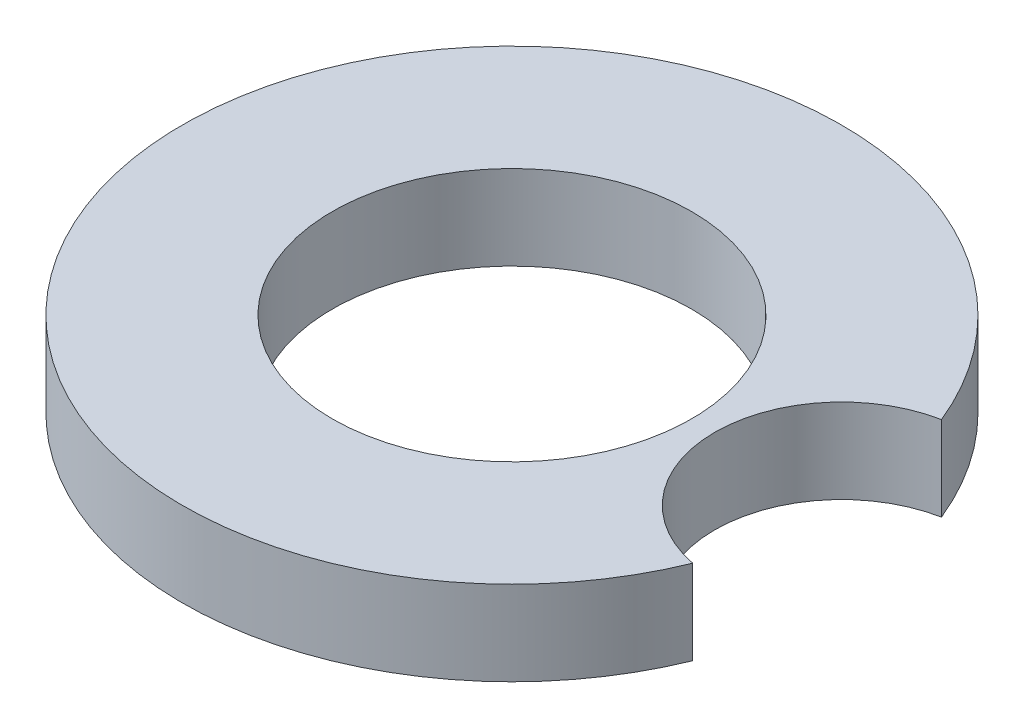
SolidWorks part; units mm, degrees
ref_plane "Front Plane" through (0, 0, 0) normal (0, 0, 1) x (1, 0, 0)
ref_plane "Top Plane" through (0, 0, 0) normal (0, 1, 0) x (1, 0, 0)
ref_plane "Right Plane" through (0, 0, 0) normal (1, 0, 0) x (0, 0, -1)
sketch "Sketch1" plane through (0, 0, 0) normal (0, 1, 0) x (1, 0, 0)
  circle A0 centre (0, 0) radius 27
  circle A1 centre (0, 0) radius 49.53
  dimension "Front_CR_ID" = 54
  dimension "Front_CR_OD" = 99.06
extrude "Boss-Extrude1" add sketch "Sketch1" along normal blind 12.7 contours A1
extrude "Cut-Extrude2" cut sketch "Sketch1<10>" along normal through all contours A0
sketch "Sketch1<10>" plane through (0, 0, 0) normal (0, 1, 0) x (1, 0, 0) same geometry as "Sketch1"
sketch "Sketch2" plane through (0, 12.7, 0) normal (0, 1, 0) x (1, 0, 0)
  circle A2 centre (49.53, 0) radius 19.05
  circle A3 centre (0, 0) radius 49.53 construction
  dimension "D1" = 38.1
extrude "Cut-Extrude3" cut sketch "Sketch2" against normal through all contours A2
ref_plane "Plane1" through (0, 6.35, 0) normal (0, -1, 0) x (-1, 0, 0)
equation "\"Motor_OD\" = 54mm"
equation "\"Aft_Section_Length\" = 30in"
equation "\"Mid_Coupler_Length\" = 12in"
equation "\"AB_Coupler_OD_Length\"= 1in"
equation "\"AB_Coupling_Section_Length\"= 0.375in"
equation "\"AB_Coupler_Length\"= \"AB_Coupler_OD_Length\" + \"AB_Coupling_Section_Length\" * 2"
equation "\"Cutout_Angle\" = 60"
equation "\"AB_Paddle_Height\" = 0.375in"
equation "\"AB_Coupler_Num_Screws\"= 4"
equation "\"Num_Cutouts\" = 4"
equation "\"AB_Coupler_OD\"= 4.024in"
equation "\"AB_Coupler_ID\"= 3.7in"
equation "\"AB_Coupler_Surface_Diameter\"= 3.899in"
equation "\"AB_Coupling_Screw_Diameter\"= 0.1065in"
equation "\"AB_Central_Bushing_Length\" = 0.75in"
equation "\"Lead_Screw_Dist\" = 2in"
equation "\"Lead_Screw_Diam\" = 0.375in"
equation "\"Lead_Screw_Length\" = \"Mid_Coupler_Length\" + 2*0.375in + 2*0.5in"
equation "\"Paddle_Pin_Offset\" = 0.25in"
equation "\"Paddle_Pin_Radius\" = 2.25*2/3in"
equation "\"Paddle_Gear_OD\" = 3.2in"
equation "\"Fwd_BKHD_From_Top\" = 18in"
equation "\"Front_CR_ID@Sketch1\"=\"Motor_OD\""
equation "\"Body_Tube_OD\"= 4.024in"
equation "\"Body_Tube_ID\"= 3.90in"
equation "\"Coupler_OD\" = 3.899in"
equation "\"Coupler_ID\" = 3.755in"
equation "\"Fwd_Section_Length\" = 25in"
equation "\"Mid_Section_Length\" = 6in"
equation "\"Aft_Upper_Tube_Length\" = 10in"
equation "\"Aft_Lower_Tube_Length\" = 18in"
equation "\"Nosecone_Coupler_Length\" = 5in"
equation "\"Avionics_Bulkhead_Thickness\" = 0.25in"
equation "\"Avionics_Bulkhead_Lip\" = 0.125in"
equation "\"Avionics_Board_Length\" = \"Mid_Coupler_Length\" - 2*\"Avionics_Bulkhead_Lip\""
equation "\"Lead_Screw_Hole_Diam\" = (27/64)*1in"
equation "\"Front_CR_OD@Sketch1\"=\"Body_Tube_ID\""
equation "\"Centering_Ring_Cutout_Dia\"=1.5in"
equation "\"D1@Sketch2\"=\"Centering_Ring_Cutout_Dia\""
